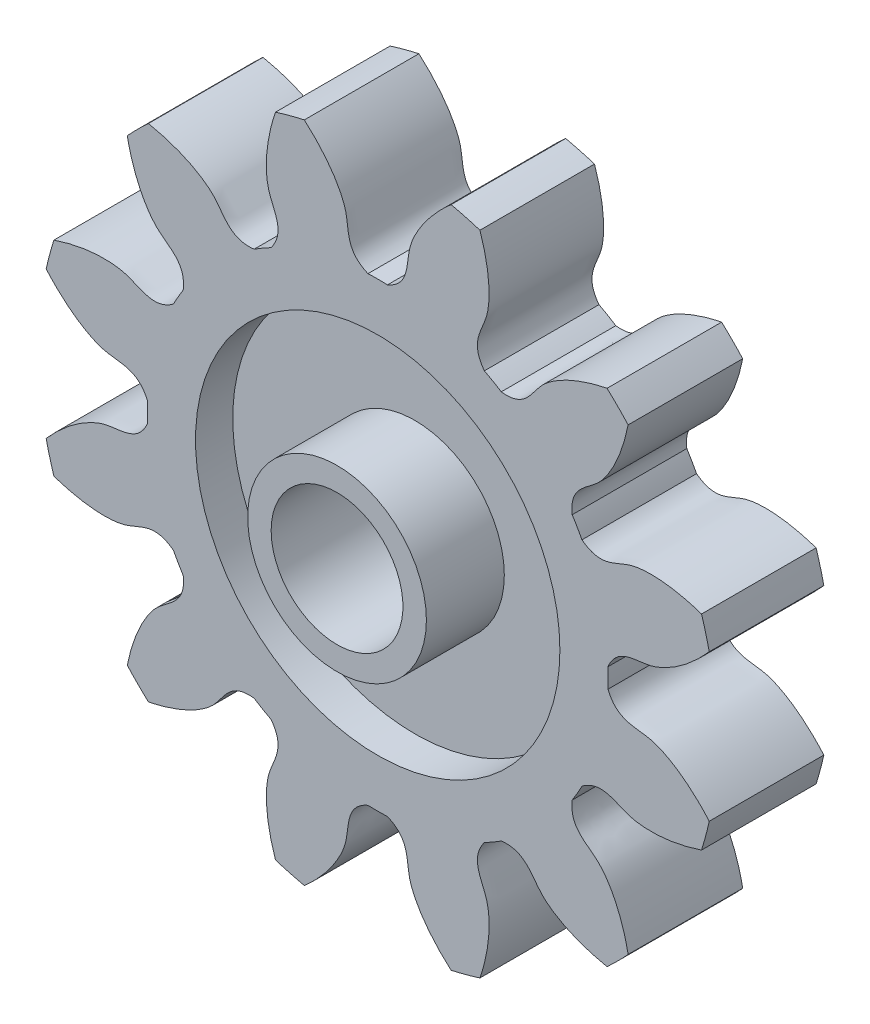
SolidWorks part; units mm, degrees
material "黄铜"
ref_plane "前视基准面" through (0, 0, 0) normal (0, 0, 1) x (1, 0, 0)
ref_plane "上视基准面" through (0, 0, 0) normal (0, 1, 0) x (1, 0, 0)
ref_plane "右视基准面" through (0, 0, 0) normal (1, 0, 0) x (0, 0, -1)
sketch "草图1" plane through (0, 0, 0) normal (0, 0, 1) x (1, 0, 0)
  circle A0 centre (0, 0) radius 11.8533
extrude "凸台-拉伸1" add sketch "草图1" along normal blind 4
ref_axis "基准轴1" through (0, 0, -0.2) along (0, 0, 1)
sketch "草图2" plane through (0, 0, 0) normal (0, 0, 1) x (1, 0, 0)
  line L0 (0, 0) -> (0, 11.8533) construction
  circle A0 centre (0, 0) radius 11.8533 construction
  arc A1 (0.3401, 8.0361) -> (-0.3401, 8.0361) centre (0, 0) ccw
  arc A2 (5.9226, 13.3688) -> (-5.9226, 13.3688) centre (0, 0) ccw
  spline S0 degree 3 poles (0.3401, 8.0361) (1.1528, 8.3808) (0.9726, 9.0506) (1.145, 9.6342) (1.1559, 9.6688) (1.1688, 9.7068) (1.1837, 9.7481) (1.2008, 9.7926) (1.2203, 9.8404) (1.2422, 9.8912) (1.2667, 9.9451) (1.2939, 10.002) (1.324, 10.0616) (1.357, 10.1241) (1.3932, 10.1892) (1.4325, 10.2569) (1.4752, 10.327) (1.5213, 10.3995) (1.571, 10.4743) (1.6243, 10.5512) (1.6814, 10.6301) (1.7424, 10.7108) (1.8073, 10.7934) (1.8763, 10.8776) (1.9495, 10.9633) (2.0268, 11.0503) (2.1085, 11.1386) (2.1946, 11.228) (2.2852, 11.3184) (2.3803, 11.4096) (2.48, 11.5014) (2.5844, 11.5938) (2.6936, 11.6865) (2.8075, 11.7795) (2.9263, 11.8725) (3.05, 11.9654) (3.1786, 12.058) (3.3121, 12.1502) (3.4507, 12.2419) (3.5943, 12.3328) (3.7429, 12.4228) (3.8967, 12.5117) (4.0555, 12.5993) (4.2194, 12.6856) (4.3885, 12.7702) (4.5626, 12.8531) (4.7418, 12.9341) (4.9262, 13.013) (5.1156, 13.0896) (5.3101, 13.1638) (5.5785, 13.26) (5.7837, 13.3267) (5.9226, 13.3688) knots 0 0 0 0 0.218015 0.222044 0.226546 0.231522 0.236972 0.242897 0.249295 0.256167 0.263513 0.271332 0.279626 0.288394 0.297636 0.307351 0.317541 0.328204 0.339341 0.350953 0.363038 0.375597 0.38863 0.402137 0.416118 0.430573 0.445502 0.460904 0.476781 0.493132 0.509956 0.527255 0.545027 0.563273 0.581994 0.601188 0.620856 0.640998 0.661614 0.682704 0.704268 0.726305 0.748817 0.771803 0.795262 0.819196 0.843603 0.868484 0.89384 0.919669 0.945972 1 1 1 1
  spline S1 degree 3 poles (-0.3401, 8.0361) (-1.1528, 8.3808) (-0.9726, 9.0506) (-1.145, 9.6342) (-1.1559, 9.6688) (-1.1688, 9.7068) (-1.1837, 9.7481) (-1.2008, 9.7926) (-1.2203, 9.8404) (-1.2422, 9.8912) (-1.2667, 9.9451) (-1.2939, 10.002) (-1.324, 10.0616) (-1.357, 10.1241) (-1.3932, 10.1892) (-1.4325, 10.2569) (-1.4752, 10.327) (-1.5213, 10.3995) (-1.571, 10.4743) (-1.6243, 10.5512) (-1.6814, 10.6301) (-1.7424, 10.7108) (-1.8073, 10.7934) (-1.8763, 10.8776) (-1.9495, 10.9633) (-2.0268, 11.0503) (-2.1085, 11.1386) (-2.1946, 11.228) (-2.2852, 11.3184) (-2.3803, 11.4096) (-2.48, 11.5014) (-2.5844, 11.5938) (-2.6936, 11.6865) (-2.8075, 11.7795) (-2.9263, 11.8725) (-3.05, 11.9654) (-3.1786, 12.058) (-3.3121, 12.1502) (-3.4507, 12.2419) (-3.5943, 12.3328) (-3.7429, 12.4228) (-3.8967, 12.5117) (-4.0555, 12.5993) (-4.2194, 12.6856) (-4.3885, 12.7702) (-4.5626, 12.8531) (-4.7418, 12.9341) (-4.9262, 13.013) (-5.1156, 13.0896) (-5.3101, 13.1638) (-5.5785, 13.26) (-5.7837, 13.3267) (-5.9226, 13.3688) knots 0 0 0 0 0.218015 0.222044 0.226546 0.231522 0.236972 0.242897 0.249295 0.256167 0.263513 0.271332 0.279626 0.288394 0.297636 0.307351 0.317541 0.328204 0.339341 0.350953 0.363038 0.375597 0.38863 0.402137 0.416118 0.430573 0.445502 0.460904 0.476781 0.493132 0.509956 0.527255 0.545027 0.563273 0.581994 0.601188 0.620856 0.640998 0.661614 0.682704 0.704268 0.726305 0.748817 0.771803 0.795262 0.819196 0.843603 0.868484 0.89384 0.919669 0.945972 1 1 1 1
extrude "切除-拉伸1" cut sketch "草图2" along normal through all
pattern_circular "阵列(圆周)1" count 12 every 30 about axis through (0, 0, -0.2) along (0, 0, 1) of "切除-拉伸1"
sketch "草图3" plane through (0, 0, 0) normal (0, 0, 1) x (1, 0, 0)
  circle A0 centre (0, 0) radius 10.16 construction
  dimension "Dn" = 20.32
sketch "草图4" plane through (0, 0, 4) normal (0, 0, 1) x (1, 0, 0)
  circle A0 centre (0, 0) radius 6.36
  dimension "D1" = 12.72
extrude "切除-拉伸2" cut sketch "草图4" against normal blind 1.3
sketch "草图5" plane through (0, 0, 0) normal (0, 0, -1) x (-1, 0, 0)
  circle A0 centre (0, 0) radius 6.36
  dimension "D1" = 12.72
extrude "切除-拉伸3" cut sketch "草图5" against normal blind 1.3
sketch "草图6" plane through (0, 0, 2.7) normal (0, 0, 1) x (1, 0, 0)
  circle A0 centre (0, 0) radius 3.12
  dimension "D1" = 6.24
extrude "凸台-拉伸2" add sketch "草图6" along normal blind 2.72
sketch "草图7" plane through (0, 0, 1.3) normal (0, 0, -1) x (-1, 0, 0)
  circle A0 centre (0, 0) radius 3.12
  dimension "D1" = 6.24
extrude "凸台-拉伸3" add sketch "草图7" along normal blind 2.72
sketch "草图8" plane through (0, 0, -1.42) normal (0, 0, -1) x (-1, 0, 0)
  circle A0 centre (0, 0) radius 2.3
  dimension "D1" = 4.6
extrude "切除-拉伸4" cut sketch "草图8" against normal through all
cosmetic thread "装饰螺纹线1" parameters "D2"=6
